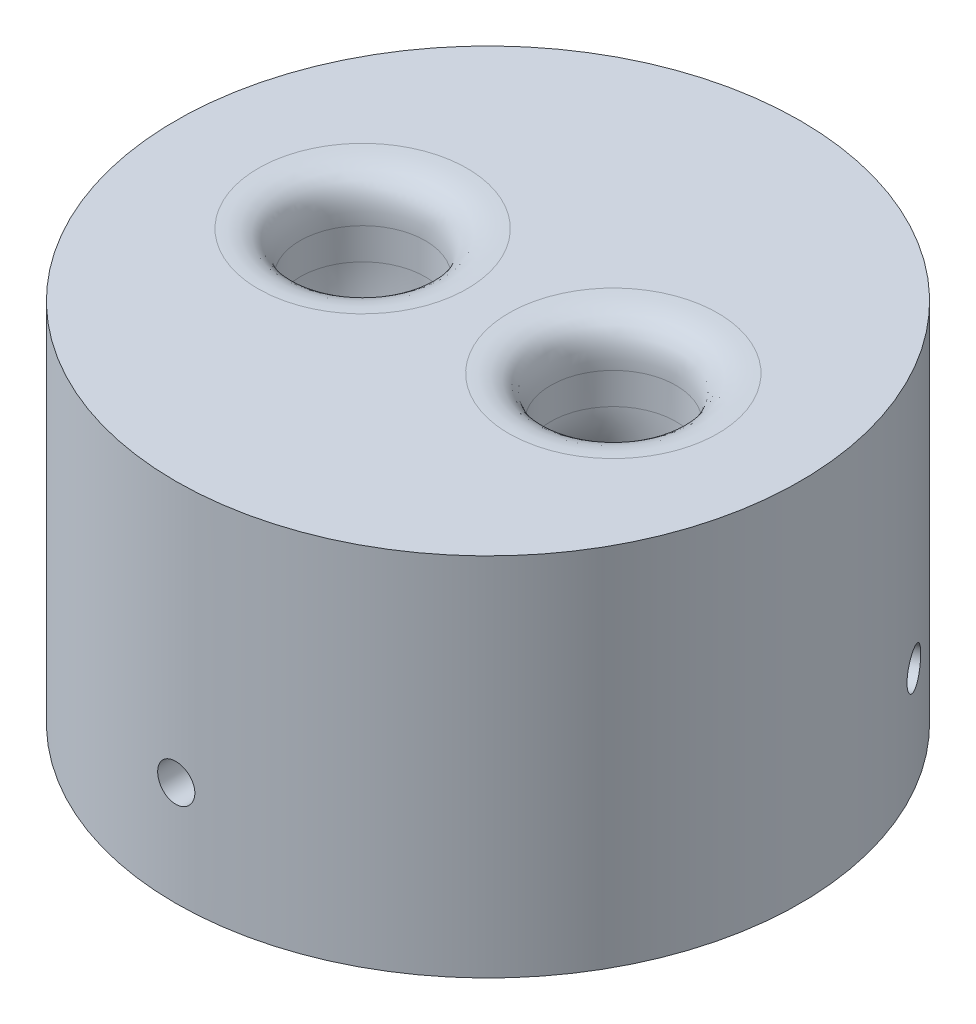
SolidWorks part; units mm, degrees
ref_plane "Front Plane" through (0, 0, 0) normal (0, 0, 1) x (1, 0, 0)
ref_plane "Top Plane" through (0, 0, 0) normal (0, 1, 0) x (1, 0, 0)
ref_plane "Right Plane" through (0, 0, 0) normal (1, 0, 0) x (0, 0, -1)
sketch "Sketch1" plane through (0, 0, 0) normal (0, 1, 0) x (1, 0, 0)
  circle A0 centre (0, 0) radius 18.9865
  dimension "D1" = 37.973
extrude "Boss-Extrude1" add sketch "Sketch1" along normal blind 17.78
sketch "Sketch2" plane through (0, 17.78, 0) normal (0, 1, 0) x (1, 0, 0)
  line L0 (0, 18.9865) -> (0, -18.9865) construction
  circle A0 centre (0, 0) radius 18.9865 construction
  circle A1 centre (-7.62, 0) radius 3.81
  dimension "D1" = 7.62
  dimension "D2" = 7.62
revolve "Cut-Revolve1" cut sketch "Sketch2" angle 360 about L0
sketch "Sketch3" plane through (0, 17.78, 0) normal (0, 1, 0) x (1, 0, 0)
  circle A0 centre (0, 0) radius 18.9865 construction
  circle A1 centre (7.62, 0) radius 3.81 construction
  circle A2 centre (-7.62, 0) radius 3.81 construction
  circle A3 centre (0, 0) radius 18.9865
  circle A4 centre (7.62, 0) radius 3.81
  circle A5 centre (-7.62, 0) radius 3.81
extrude "Boss-Extrude2" add sketch "Sketch3" along normal blind 4.445
fillet "Fillet1" radius 2.54 2 edges at (-7.62, 22.225, 3.81) (7.62, 22.225, 3.81) curvature continuous yes
ref_plane "Plane1" through (0, 0, 18.9865) normal (0, 0, 1) x (1, 0, 0)
sketch "Sketch4" plane through (0, 0, 18.9865) normal (0, 0, 1) x (1, 0, 0)
  line L0 (0, 0) -> (0, 8.1474) construction
  line L1 (-18.9865, 0) -> (18.9865, 0) construction
  point P4 (0, 6.35)
  dimension "D1" = 6.35
hole_wizard "Tap Drill for #4-40 Tap1" positions "Sketch4" profile "Sketch5" hole size "#4-40" standard "ANSI Inch"
sketch "Sketch5" plane through (0, 6.35, 18.9865) normal (1, 0, 0) x (0, -1, 0)
  line L0 (0, 0) -> (0, 10.2042)
  line L1 (0, 10.2042) -> (1.1303, 9.525)
  line L2 (1.1303, 9.525) -> (1.1303, 0)
  line L5 (1.1303, 0) -> (0, 0)
  line L10 (0, 10.2042) -> (-1.1303, 9.525) construction
  line L11 (0, -6.35) -> (0, 107.95) construction
  dimension "Hole Dia." = 2.2606
  dimension "Hole Depth" = 9.525
  dimension "Drill Angle" = 118
pattern_circular "CirPattern1" count 3 over 360 about axis through (0, 0, 0) along (0, 1, 0) of "Tap Drill for #4-40 Tap1"
